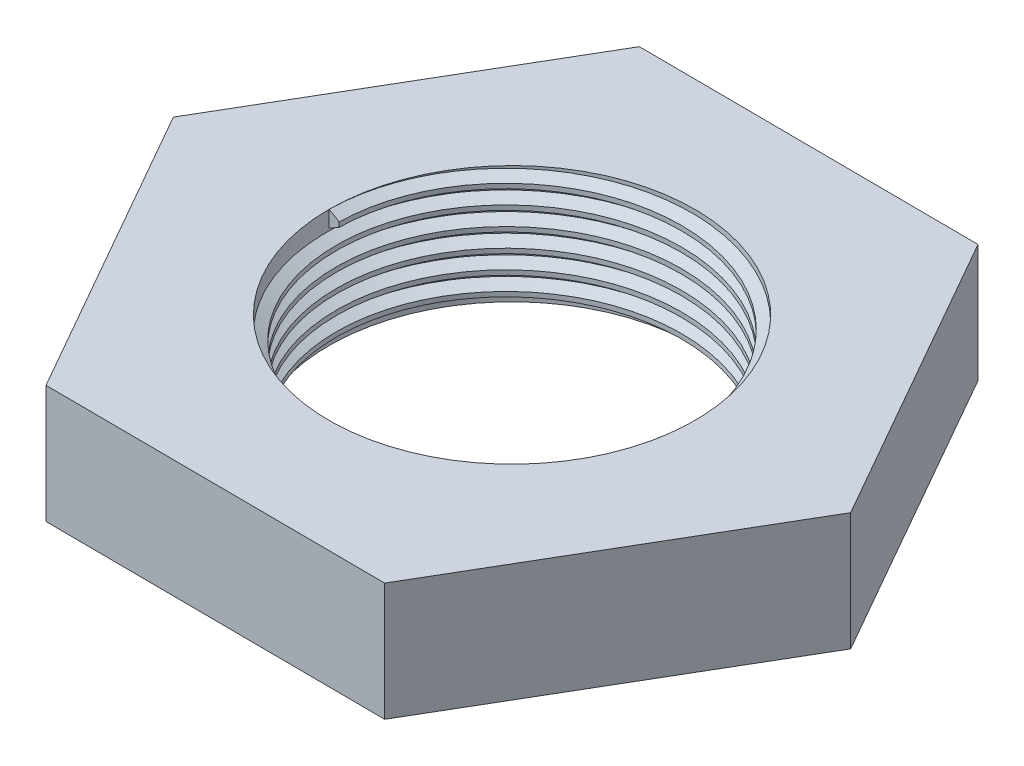
SolidWorks part; units mm, degrees
ref_plane "Front Plane" through (0, 0, 0) normal (0, 0, 1) x (1, 0, 0)
ref_plane "Top Plane" through (0, 0, 0) normal (0, 1, 0) x (1, 0, 0)
ref_plane "Right Plane" through (0, 0, 0) normal (1, 0, 0) x (0, 0, -1)
sketch "Sketch1" plane through (0, 0, 0) normal (0, 1, 0) x (1, 0, 0)
  line L1 (2.8579, -5.0165) -> (5.7734, -0.0333)
  line L2 (5.7734, -0.0333) -> (2.9155, 4.9833)
  line L3 (2.9155, 4.9833) -> (-2.8579, 5.0165)
  line L4 (-2.8579, 5.0165) -> (-5.7734, 0.0333)
  line L5 (-5.7734, 0.0333) -> (-2.9155, -4.9833)
  line L6 (-2.9155, -4.9833) -> (2.8579, -5.0165)
  circle A0 centre (0, 0) radius 5 construction
  circle A1 centre (0, 0) radius 3.1
  dimension "D3" = 6.2
  dimension "D1" = 10
  dimension "D2" = 11.5468
extrude "Boss-Extrude1" add sketch "Sketch1" along normal blind 2
thread "Thread1" pitch 0.3175 method extrude profile "Thread Profile1" start angle 0, offset 0, length 1.8, pitch 0.3175, diameter 6.2
ref_plane "Plane1" through (-3.1, 2, 0) normal (0, 0, 1) x (-1, 0, 0)
sketch "Thread Profile1" plane through (-3.1, 2, 0) normal (0, 0, 1) x (-1, 0, 0)
  line L0 (0, 0) -> (0, 0.3175) construction
  line L11 (0, 0) -> (0, 0.2778)
  line L12 (0, 0.2778) -> (-0.1719, 0.1786)
  line L13 (-0.1719, 0.1786) -> (-0.1719, 0.0992)
  line L15 (-0.1719, 0.0992) -> (0, 0)
  line L17 (-0.1719, 0.1389) -> (0, 0.1389) construction
  point P2 (0, 0)
  dimension "Pitch" = 0.3175
  dimension "Profile_Angle" = 60
  dimension "Profile_Land" = 0.0794
  dimension "Profile_Height" = 0.1719
